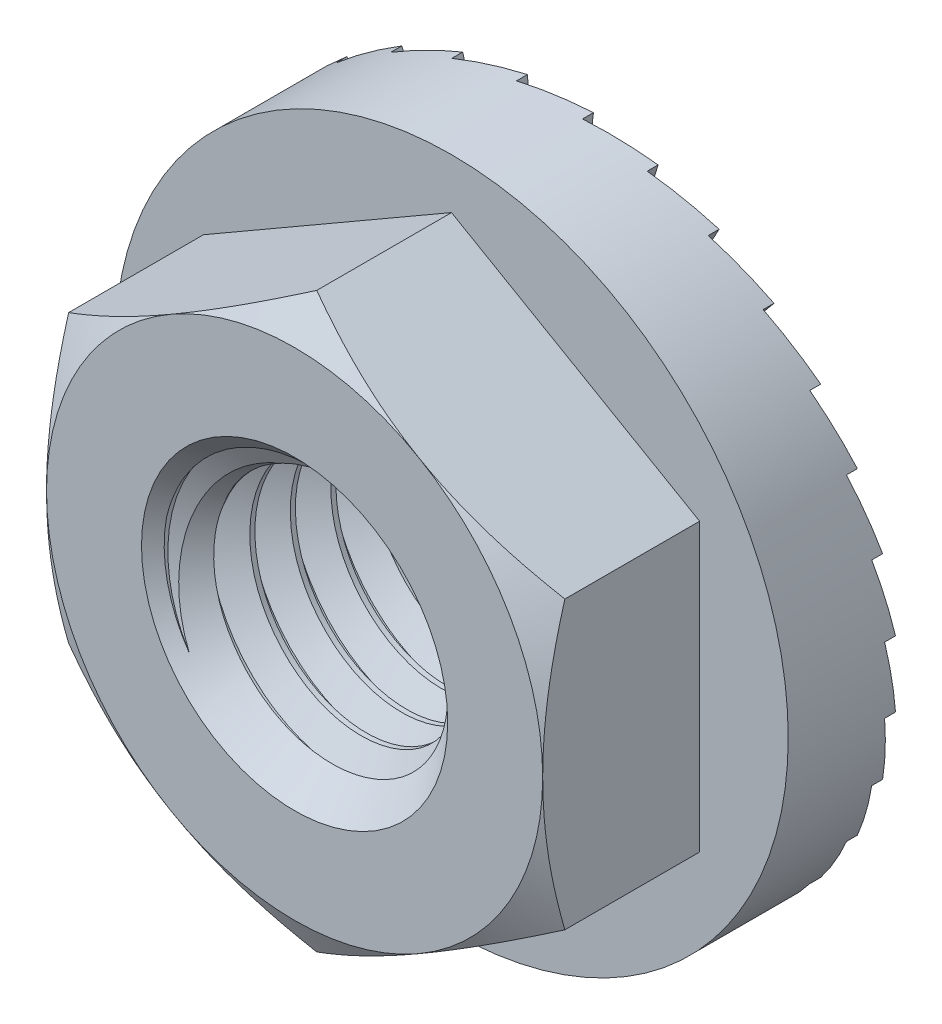
SolidWorks part; units mm, degrees
material "AISI 304"
ref_plane "Front Plane" through (0, 0, 0) normal (0, 0, 1) x (1, 0, 0)
ref_plane "Top Plane" through (0, 0, 0) normal (0, 1, 0) x (1, 0, 0)
ref_plane "Right Plane" through (0, 0, 0) normal (1, 0, 0) x (0, 0, -1)
sketch "Sketch1" plane through (0, 0, 0) normal (0, 0, 1) x (1, 0, 0)
  line L1 (0, 6.4158) -> (-5.5563, 3.2079)
  line L2 (-5.5563, 3.2079) -> (-5.5563, -3.2079)
  line L3 (-5.5563, -3.2079) -> (0, -6.4158)
  line L4 (0, -6.4158) -> (5.5562, -3.2079)
  line L5 (5.5562, -3.2079) -> (5.5562, 3.2079)
  line L6 (5.5562, 3.2079) -> (0, 6.4158)
  circle A0 centre (0, 0) radius 5.5563 construction
  dimension "Hex" = 11.1125
extrude "Extrude1" add sketch "Sketch1" against normal blind 5.9531
sketch "Sketch13" plane through (0, 0, -5.9531) normal (0, 0, -1) x (-1, 0, 0)
  circle A0 centre (0, 0) radius 7.5406
  dimension "Flange od" = 15.0812
extrude "Extrude3" add sketch "Sketch13" against normal blind 2.4384
sketch "Sketch2" plane through (0, 0, 0) normal (0, 0, 1) x (1, 0, 0)
  circle A0 centre (0, 0) radius 5.5563 construction
  circle A1 centre (0, 0) radius 5.5563
extrude "Cut-Extrude1" cut sketch "Sketch2" against normal through all draft 60 flip side to cut
sketch "Sketch4" plane through (0, 0, 0) normal (0, 0, 1) x (1, 0, 0)
  circle A0 centre (0, 0) radius 3.175
  dimension "Thread Dia" = 6.35
extrude "Cut-Extrude3" cut sketch "Sketch4" against normal through all
sketch "Sketch7" plane through (0, 0, 0) normal (0, 0, 1) x (1, 0, 0)
  circle A4 centre (0, 0) radius 3.429
  circle A5 centre (0, 0) radius 3.429
  dimension "D1" = 0.254
sketch "Sketch8" plane through (0, 0, -5.9531) normal (0, 0, -1) x (-1, 0, 0)
  circle A1 centre (0, 0) radius 3.429
  circle A2 centre (0, 0) radius 3.429 construction
sketch "Sketch5" plane through (0, 0, 0) normal (0, 0, 1) x (1, 0, 0)
  circle A0 centre (0, 0) radius 3.175 construction
  circle A1 centre (0, 0) radius 3.175
curve "Helix/Spiral1" pitch 0.9071 height 6.8603 turns 7.5625 parameters "pitch"=0.9071
sketch "Sketch9" plane through (0, 0, 0) normal (1, 0, 0) x (0, 0, -1)
  line L0 (-0.4536, 3.175) -> (-0.3402, 3.175)
  line L1 (-0.3402, 3.175) -> (0, 2.5858)
  line L2 (-0.4536, 3.175) -> (-0.7937, 2.5858)
  line L3 (-0.7937, 2.5858) -> (0, 2.5858)
  line L4 (-0.3969, 3.175) -> (-0.3969, 2.5858) construction
  line L5 (-0.6237, 2.8804) -> (-0.1701, 2.8804) construction
  line L7 (0, 2.5858) -> (0, 3.175) construction
  line L8 (0, 3.175) -> (0, -3.175) construction
  dimension "D1" = 0.1134
  dimension "D2" = 0.4536
  dimension "D3" = 60
sketch "Sketch12" plane through (0, 0, 0) normal (0, 0, 1) x (1, 0, 0)
  circle A0 centre (0, 0) radius 2.5858
  circle A1 centre (0, 0) radius 3.175 construction
  circle A2 centre (0, 0) radius 3.175
extrude "Extrude2" add sketch "Sketch12" against normal up to surface (5.9531 mm away)
sweep "Cut-Sweep1" cut profiles "Sketch9" path "Helix/Spiral1" align with end faces yes
extrude "Cut-Extrude6" cut sketch "Sketch7" against normal through all draft 45
extrude "Cut-Extrude7" cut sketch "Sketch8" against normal through all draft 45
sketch "Sketch14" plane through (0, 0, -5.9531) normal (0, 0, -1) x (-1, 0, 0)
  circle A4 centre (0, 0) radius 5.461
  circle A5 centre (0, 0) radius 5.461
  dimension "D1" = 2.032
extrude "Cut-Extrude8" cut sketch "Sketch14" against normal blind 0.2438 flip side to cut
sketch "Sketch15" plane through (0, 0, -5.7093) normal (0, 0, -1) x (-1, 0, 0)
  line L0 (-0.5353, 5.4347) -> (-0.7391, 7.5043)
  line L1 (0.5353, 5.4347) -> (0.7391, 7.5043)
  line L2 (0, 0) -> (0.5353, 5.4347) construction
  line L3 (0, 0) -> (-0.5353, 5.4347) construction
  circle A0 centre (0, 0) radius 7.5406 construction
  circle A1 centre (0, 0) radius 5.461 construction
  arc A2 (0.7391, 7.5043) -> (-0.7391, 7.5043) centre (0, 0) ccw
  arc A3 (0.5353, 5.4347) -> (-0.5353, 5.4347) centre (0, 0) ccw
  dimension "D1" = 11.25
extrude "Extrude4" add sketch "Sketch15" along normal up to surface (0.2438 mm away) separate body up to face at (-3.429, 0, -5.9531)
sketch "Sketch16" plane through (0, 0, 0) normal (0, 1, 0) x (1, 0, 0)
  line L0 (-0.7391, 5.7093) -> (0.7391, 5.9531)
  line L4 (-0.7391, 5.7093) -> (0.7391, 5.7093)
  line L5 (0.7391, 5.7093) -> (0.7391, 5.9531)
  line L6 (0.7391, 5.9531) -> (-0.7391, 5.9531)
  line L7 (-0.7391, 5.9531) -> (-0.7391, 5.7093)
  line L8 (-0.7391, 5.7093) -> (0.7391, 5.7093) construction
  line L9 (0.7391, 5.7093) -> (0.7391, 5.9531) construction
  line L10 (0.7391, 5.9531) -> (-0.7391, 5.9531)
  line L11 (-0.7391, 5.9531) -> (-0.7391, 5.7093)
  dimension "D1" = 0
extrude "Cut-Extrude9" cut sketch "Sketch16" along normal through all
pattern_circular "CirPattern1" count 32 over 360 about axis through (0, 0, 0) along (0, 0, 1) of bodies 119
combine bodies "Combine1" operation type add bodies to combine 117 119 120 121 122 123 124 125 126 127 128 129 130 131 132 133 134 135 136 137 139 140 141 142 143 144 145 146 147 148 149 150 151
sketch "Sketch17" plane through (0, 0, 0) normal (1, 0, 0) x (0, 0, -1)
  line L0 (5.9531, 7.5406) -> (5.9531, -7.5406) construction
  line L1 (3.5147, 7.5406) -> (3.5147, -7.5406) construction
  dimension "D1" = 2.4384
sketch "Sketch18" plane through (0, 0, -3.5147) normal (0, 0, 1) x (1, 0, 0)
  circle A0 centre (0, 0) radius 7.5406
  circle A1 centre (0, 0) radius 7.5406 construction
equation "\"D2@Sketch9\" = \"pitch@Helix/Spiral1\"*.5"
equation "\"D3@Helix/Spiral1\" = \"pitch@Helix/Spiral1\"+\"Height@Extrude1\""
equation "\"D1@Sketch9\" = \"pitch@Helix/Spiral1\"*.125"
equation "\"D1@Cut-Extrude8\" = \"flange thickness@Extrude3\"*.1"
equation "\"D1@Sketch17\" = \"flange thickness@Extrude3\""
